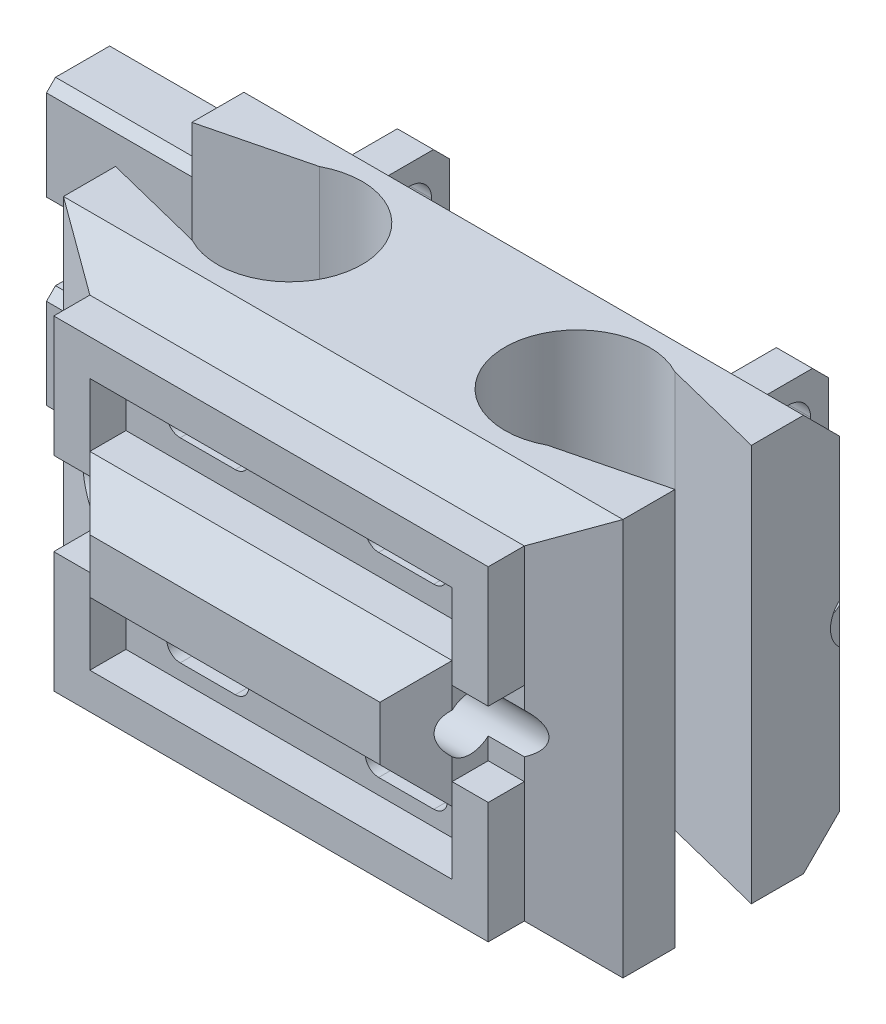
SolidWorks part; units mm, degrees
ref_plane "Front Plane" through (0, 0, 0) normal (0, 0, 1) x (1, 0, 0)
ref_plane "Top Plane" through (0, 0, 0) normal (0, 1, 0) x (1, 0, 0)
ref_plane "Right Plane" through (0, 0, 0) normal (1, 0, 0) x (0, 0, -1)
sketch "Base" plane through (0, 0, 0) normal (0, 0, 1) x (1, 0, 0)
  line L1 (0, 0) -> (15.5, 0)
  line L2 (0, 0) -> (0, 11)
  line L3 (0, 11) -> (15.5, 11)
  line L4 (15.5, 0) -> (15.5, 11)
  dimension "D1" = 15.5
  dimension "D2" = 11
extrude "Phalange shape" add sketch "Base" along normal blind 7
chamfer "Chamfer4" distance 1 angle 45 2 edges at (7.75, 11, 7) (7.75, 0, 7)
chamfer "Chamfer5" distance 1 angle 60 2 edges at (0, 5.5, 7) (15.5, 5.5, 7)
chamfer "Chamfer6" distance 1 angle 45 2 edges at (7.75, 11, 0) (7.75, 0, 0)
sketch "Sketch8" plane through (0, 0, 7) normal (0, 0, 1) x (1, 0, 0)
  line L0 (13.7679, 5.5) -> (1.7321, 5.5) construction
  line L1 (13.7679, 1) -> (13.7679, 10) construction
  line L2 (1.7321, 10) -> (1.7321, 1) construction
  line L3 (7.75, 1) -> (7.75, 10) construction
  line L4 (1.7321, 1) -> (13.7679, 1) construction
  line L5 (13.7679, 10) -> (1.7321, 10) construction
  line L6 (2.7321, 3.75) -> (2.7321, 7.25)
  line L7 (12.7679, 7.25) -> (2.7321, 7.25)
  line L8 (12.7679, 7.25) -> (12.7679, 3.75)
  line L9 (12.7679, 3.75) -> (2.7321, 3.75)
  point P17 (2.7321, 5.5)
  point P18 (12.7679, 5.5)
  dimension "D1" = 1.75
  dimension "D2" = 1
  dimension "D3" = 1
extrude "Ligament inside" add sketch "Sketch8" along normal blind 2
sketch "Sketch9" plane through (12.7679, 0, 0) normal (1, 0, 0) x (0, 0, -1)
  line L0 (-9, 5.5) -> (-7, 5.5) construction
  line L1 (-9, 3.75) -> (-9, 7.25) construction
  line L2 (-7, 3.75) -> (-7, 7.25) construction
  circle A0 centre (-7.5, 5.5) radius 0.75
  dimension "D1" = 1.5
  dimension "D2" = 1.5
extrude "Ligament inside hole" cut sketch "Sketch9" against normal blind 34.5 and the other way blind 4.2544
chamfer "Chamfer9" distance 1 angle 45 4 edges at (2.7321, 5.5, 9) (7.75, 7.25, 9) (12.7679, 5.5, 9) (7.75, 3.75, 9)
sketch "Sketch10" plane through (0, 0, 0) normal (0, 0, -1) x (-1, 0, 0)
  line L0 (-7.75, 1) -> (-7.75, 10) construction
  line L1 (-15.5, 1) -> (0, 1) construction
  line L2 (0, 10) -> (-15.5, 10) construction
  line L3 (0, 5.5) -> (-15.5, 5.5) construction
  line L4 (0, 10) -> (0, 1) construction
  line L5 (-15.5, 1) -> (-15.5, 10) construction
  line L6 (-1, 7.25) -> (-14.5, 7.25)
  line L8 (-1, 7.25) -> (-1, 3.75)
  line L9 (-1, 3.75) -> (-14.5, 3.75)
  line L10 (-14.5, 7.25) -> (-14.5, 3.75)
  point P17 (-14.5, 5.5)
  point P18 (-1, 5.5)
  dimension "D1" = 1.75
  dimension "D2" = 1
  dimension "D3" = 1
extrude "Ligament outside" add sketch "Sketch10" along normal blind 2
sketch "Sketch11" plane through (1, 0, 0) normal (-1, 0, 0) x (0, 0, 1)
  line L0 (-2, 5.5) -> (0, 5.5) construction
  line L1 (-2, 3.75) -> (-2, 7.25) construction
  line L2 (0, 3.75) -> (0, 7.25) construction
  circle A0 centre (-0.5, 5.5) radius 0.75
  dimension "D1" = 1.5
  dimension "D2" = 1.5
extrude "Ligament outside hole" cut sketch "Sketch11" against normal blind 36.5 and the other way blind 2.5
chamfer "Chamfer11" distance 1 angle 45 4 edges at (7.75, 7.25, -2) (1, 5.5, -2) (7.75, 3.75, -2) (14.5, 5.5, -2)
sketch "Tendon extrude" plane through (0, 0, 0) normal (0, -1, 0) x (1, 0, 0)
  line L0 (7.75, 6) -> (7.75, -3.9632) construction
  line L1 (15.5, 6) -> (0, 6) construction
  line L2 (0, 3.5) -> (21.7648, 3.5) construction
  line L3 (0, 6) -> (0, 1) construction
  line L4 (3.77, 4) -> (-2.23, 4)
  line L5 (3.77, 1.5) -> (-2.23, 3)
  line L6 (3.77, 4) -> (3.77, 3)
  line L7 (3.77, 3) -> (-2.23, 3)
  line L8 (-2.23, 4) -> (-2.23, 3)
  line L9 (3.77, 5.5) -> (-2.23, 4)
  line L10 (11.73, 4) -> (11.73, 3)
  line L11 (11.73, 1.5) -> (17.73, 3)
  line L12 (11.73, 3) -> (17.73, 3)
  line L13 (11.73, 3) -> (11.73, 4)
  line L14 (11.73, 4) -> (17.73, 4)
  line L15 (17.73, 3) -> (17.73, 4)
  line L16 (17.73, 4) -> (11.73, 5.5)
  circle A0 centre (3.77, 3.5) radius 2
  circle A1 centre (11.73, 3.5) radius 2
  point P16 (-2.23, 3.5)
  dimension "D1" = 4
  dimension "D2" = 3.77
  dimension "D3" = 1
  dimension "D4" = 6
  dimension "D5" = 6
extrude "Tendons fixation" cut sketch "Tendon extrude" against normal blind 11
sketch "Sketch12" plane through (0, 0, 0) normal (0, 0, -1) x (-1, 0, 0)
  line L0 (-7.75, 10) -> (-7.75, 1) construction
  line L1 (0, 10) -> (-15.5, 10) construction
  line L2 (-15.5, 1) -> (0, 1) construction
  line L3 (-2, 4.75) -> (-2, 6.25) construction
  line L4 (-2, 10) -> (-3, 10)
  line L5 (-2, 10) -> (-2, 6.25)
  line L6 (-2, 6.25) -> (-3, 6.25)
  line L7 (-3, 10) -> (-3, 6.25)
  line L8 (-2, 4.75) -> (-3, 4.75)
  line L9 (-2, 4.75) -> (-2, 1)
  line L10 (-2, 1) -> (-3, 1)
  line L11 (-3, 4.75) -> (-3, 1)
  line L12 (-2, 6.25) -> (-13.5, 6.25) construction
  line L13 (-13.5, 4.75) -> (-2, 4.75) construction
  line L14 (-13.5, 1) -> (-12.5, 1)
  line L15 (-13.5, 4.75) -> (-13.5, 1)
  line L16 (-12.5, 4.75) -> (-12.5, 1)
  line L17 (-13.5, 4.75) -> (-12.5, 4.75)
  line L18 (-13.5, 10) -> (-12.5, 10)
  line L19 (-12.5, 10) -> (-12.5, 6.25)
  line L20 (-13.5, 6.25) -> (-12.5, 6.25)
  line L21 (-13.5, 10) -> (-13.5, 6.25)
  dimension "D2" = 1
extrude "Boss-Extrude7" add sketch "Sketch12" along normal blind 2
sketch "Sketch13" plane through (2, 0, 0) normal (-1, 0, 0) x (0, 0, 1)
  line L0 (-0.6, 8.85) -> (-0.6, 7.85) construction
  line L1 (0, 8.85) -> (0, 7.85)
  line L2 (-1.2, 8.85) -> (-1.2, 7.85)
  line L4 (0, 3.75) -> (-1, 3.75) construction
  line L5 (0, 7.25) -> (0, 10) construction
  line L6 (-1, 7.25) -> (0, 7.25) construction
  line L7 (-0.6, 3.15) -> (-0.6, 2.15) construction
  line L8 (0, 3.15) -> (0, 2.15)
  line L9 (-1.2, 3.15) -> (-1.2, 2.15)
  arc A0 (0, 8.85) -> (-1.2, 8.85) centre (-0.6, 8.85) ccw
  arc A1 (-1.2, 7.85) -> (0, 7.85) centre (-0.6, 7.85) ccw
  arc A2 (0, 3.15) -> (-1.2, 3.15) centre (-0.6, 3.15) ccw
  arc A3 (-1.2, 2.15) -> (0, 2.15) centre (-0.6, 2.15) ccw
  point P2 (-0.6, 8.35)
  point P7 (-0.6, 2.65)
  dimension "D1" = 0
  dimension "D2" = 0.6
  dimension "D3" = 0.6
  dimension "D4" = 0.6
  dimension "D5" = 1
extrude "Touch sensor wire gauge" cut sketch "Sketch13" against normal blind 12
chamfer "Chamfer12" distance 0.3 angle 45 8 edges at (12.5, 8.125, -2) (13.5, 8.125, -2) (13.5, 2.875, -2) (12.5, 2.875, -2) (2, 2.875, -2) (3, 2.875, -2) (3, 8.125, -2) (2, 8.125, -2)
chamfer "Chamfer13" distance 0.75 angle 45 4 edges at (13, 10, -2) (13, 1, -2) (2.5, 1, -2) (2.5, 10, -2)
sketch "Sketch15" plane through (0, 0, 0) normal (-1, 0, 0) x (0, 0, 1)
  line L0 (0.25, 5.5) -> (2.4425, 5.5) construction
  line L1 (2.4425, 11) -> (2.4425, 0) construction
  line L2 (0, 9.5) -> (2, 9.5)
  line L3 (0, 4.5) -> (2, 4.5)
  line L4 (0, 4.5) -> (0, 1.5)
  line L5 (0, 1.5) -> (2, 1.5)
  line L6 (2, 4.5) -> (2, 1.5)
  line L7 (2, 6.5) -> (2, 9.5)
  line L8 (0, 6.5) -> (0, 9.5)
  line L9 (0, 6.5) -> (2, 6.5)
  line L12 (0, 4.941) -> (0, 1) construction
  arc A0 (0, 4.941) -> (0, 6.059) centre (-0.5, 5.5) ccw construction
  dimension "D1" = 2
  dimension "D3" = 3
  dimension "D4" = 1
extrude "Boss-Extrude8" add sketch "Sketch15" along normal blind 4.47
chamfer "Chamfer14" distance 0.25 angle 45 8 edges at (-2.235, 6.5, 2) (-2.235, 9.5, 2) (-2.235, 9.5, 0) (-2.235, 6.5, 0) (-2.235, 4.5, 0) (-2.235, 4.5, 2) (-2.235, 1.5, 2) (-2.235, 1.5, 0)
chamfer "Chamfer15" distance 0.5 angle 45 4 edges at (0, 9.5, 1) (0, 1.5, 1) (0, 4.5, 1) (0, 6.5, 1)
sketch "Sketch16" plane through (0, 0, 7) normal (0, 0, 1) x (1, 0, 0)
  line L0 (13.7679, 1) -> (13.7679, 4.941) construction
  line L1 (1.7321, 1) -> (13.7679, 1)
  line L2 (1.7321, 1) -> (1.7321, 2)
  line L3 (1.7321, 2) -> (13.7679, 2)
  line L4 (13.7679, 1) -> (13.7679, 2)
  line L5 (12.7679, 3.75) -> (12.7679, 4.941) construction
  line L6 (12.7679, 4.3455) -> (13.7679, 4.3455)
  line L7 (12.7679, 4.3455) -> (12.7679, 2)
  line L8 (12.7679, 2) -> (13.7679, 2)
  line L9 (13.7679, 4.3455) -> (13.7679, 2)
  line L10 (2.7321, 4.941) -> (2.7321, 3.75) construction
  line L11 (2.7321, 4.3455) -> (1.7321, 4.3455)
  line L12 (2.7321, 4.3455) -> (2.7321, 2)
  line L13 (2.7321, 2) -> (1.7321, 2)
  line L14 (1.7321, 4.3455) -> (1.7321, 2)
  line L15 (13.7679, 6.059) -> (13.7679, 10) construction
  line L16 (1.7321, 10) -> (13.7679, 10)
  line L17 (1.7321, 10) -> (1.7321, 9)
  line L18 (1.7321, 9) -> (13.7679, 9)
  line L19 (13.7679, 10) -> (13.7679, 9)
  line L20 (2.7321, 7.25) -> (2.7321, 6.059) construction
  line L21 (2.7321, 6.6545) -> (1.7321, 6.6545)
  line L22 (2.7321, 6.6545) -> (2.7321, 9)
  line L23 (2.7321, 9) -> (1.7321, 9)
  line L24 (1.7321, 6.6545) -> (1.7321, 9)
  line L25 (12.7679, 6.059) -> (12.7679, 7.25) construction
  line L26 (12.7679, 6.6545) -> (13.7679, 6.6545)
  line L27 (12.7679, 6.6545) -> (12.7679, 9)
  line L28 (12.7679, 9) -> (13.7679, 9)
  line L29 (13.7679, 6.6545) -> (13.7679, 9)
  line M2 (1.7321, 4.941) -> (1.7321, 1)
  line M3 (1.7321, 1) -> (13.7679, 1)
  line M4 (13.7679, 1) -> (13.7679, 4.941)
  line M6 (12.7679, 4.941) -> (12.7679, 3.75)
  line M8 (2.7321, 3.75) -> (2.7321, 4.941)
extrude "Boss-Extrude9" add sketch "Sketch16" along normal blind 1 contours L12 L11 L3 M8 M2 | L3 M2 M3 M4 | L7 L3 L6 M6 M4 | L26 L29 L18 L27 | L19 L16 L17 L18 | L24 L21 L22 L18
sketch "Sketch17" plane through (0, 0, 7) normal (0, 0, 1) x (1, 0, 0)
  line L0 (4.2345, 8.2) -> (5.7625, 8.2) construction
  line L1 (4.2345, 8.5716) -> (5.7625, 8.5716)
  line L2 (4.2345, 7.8284) -> (5.7625, 7.8284)
  line L3 (9.7336, 8.2) -> (11.2616, 8.2) construction
  line L4 (9.7336, 8.5716) -> (11.2616, 8.5716)
  line L5 (9.7336, 7.8284) -> (11.2616, 7.8284)
  line L6 (4.2345, 2.8) -> (5.7625, 2.8) construction
  line L7 (4.2345, 3.1716) -> (5.7625, 3.1716)
  line L8 (4.2345, 2.4284) -> (5.7625, 2.4284)
  line L9 (9.7336, 2.8) -> (11.2616, 2.8) construction
  line L10 (9.7336, 3.1716) -> (11.2616, 3.1716)
  line L11 (9.7336, 2.4284) -> (11.2616, 2.4284)
  line L12 (2.7321, 9) -> (12.7679, 9) construction
  line L13 (2.7321, 2) -> (12.7679, 2) construction
  arc A0 (4.2345, 8.5716) -> (4.2345, 7.8284) centre (4.2345, 8.2) ccw
  arc A1 (5.7625, 7.8284) -> (5.7625, 8.5716) centre (5.7625, 8.2) ccw
  arc A2 (9.7336, 8.5716) -> (9.7336, 7.8284) centre (9.7336, 8.2) ccw
  arc A3 (11.2616, 7.8284) -> (11.2616, 8.5716) centre (11.2616, 8.2) ccw
  arc A4 (4.2345, 3.1716) -> (4.2345, 2.4284) centre (4.2345, 2.8) ccw
  arc A5 (5.7625, 2.4284) -> (5.7625, 3.1716) centre (5.7625, 2.8) ccw
  arc A6 (9.7336, 3.1716) -> (9.7336, 2.4284) centre (9.7336, 2.8) ccw
  arc A7 (11.2616, 2.4284) -> (11.2616, 3.1716) centre (11.2616, 2.8) ccw
  point P2 (4.9985, 8.2)
  point P7 (10.4976, 8.2)
  point P16 (4.9985, 2.8)
  point P21 (10.4976, 2.8)
  dimension "D1" = 0.8
  dimension "D2" = 0.8
extrude "Cut-Extrude1" cut sketch "Sketch17" against normal blind 1
